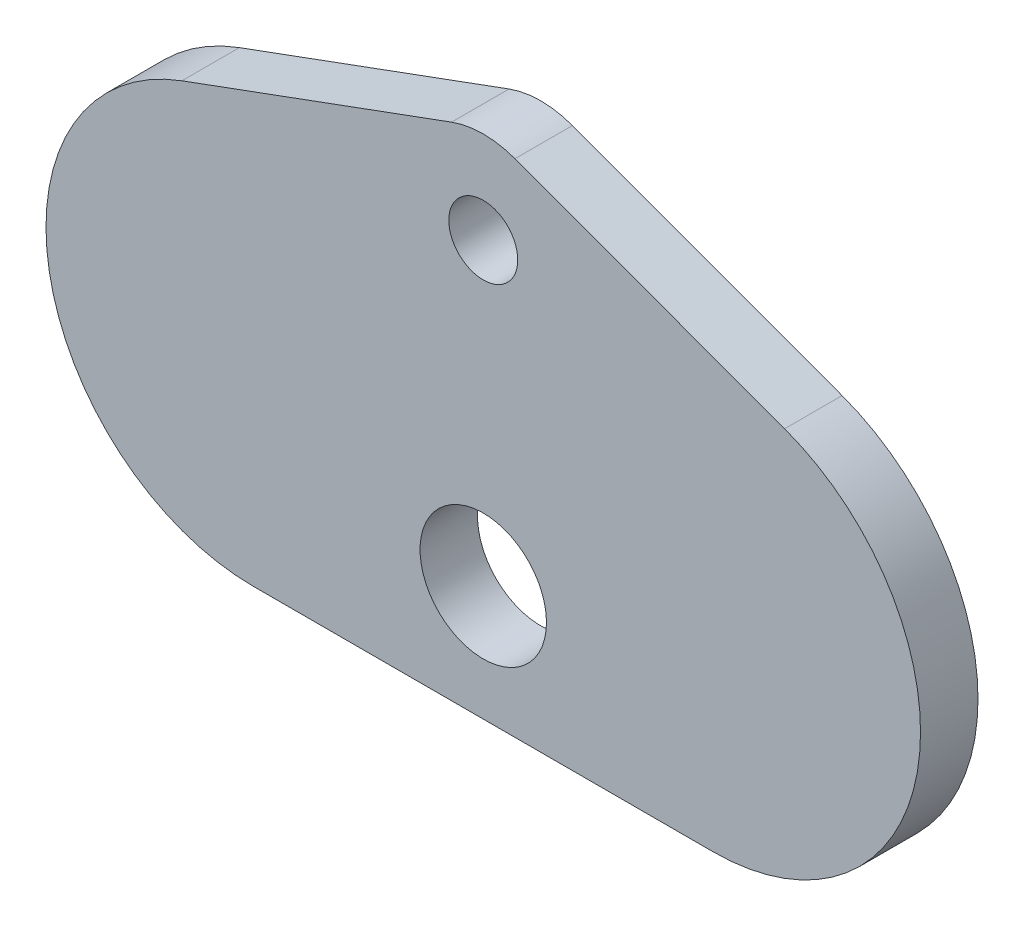
SolidWorks part; units mm, degrees
ref_plane "Płaszczyzna przednia" through (0, 0, 0) normal (0, 0, 1) x (1, 0, 0)
ref_plane "Płaszczyzna górna" through (0, 0, 0) normal (0, 1, 0) x (1, 0, 0)
ref_plane "Płaszczyzna prawa" through (0, 0, 0) normal (1, 0, 0) x (0, 0, -1)
sketch "Sketch1" plane through (0, 0, 0) normal (0, 0, 1) x (1, 0, 0)
  line L0 (-40, -52.095) -> (40, -52.095) construction
  line L1 (0, -52.095) -> (0, 0) construction
  line L2 (-40, -52.095) -> (40, -52.095) construction
  line L3 (-40, -16) -> (40, -16)
  line L4 (-40, -88.19) -> (40, -88.19)
  line L5 (-5.5152, -0.9806) -> (-52.4418, -18.2121)
  line L6 (5.5152, -0.9806) -> (52.4418, -18.2121)
  circle A0 centre (-40, -52.095) radius 26.095
  circle A1 centre (40, -52.095) radius 26.095
  circle A4 centre (0, -16) radius 6
  arc A7 (-40, -16) -> (-40, -88.19) centre (-40, -52.095) ccw
  arc A8 (40, -88.19) -> (40, -16) centre (40, -52.095) ccw
  circle A9 centre (0, -16) radius 16
  circle A10 centre (0, -68.1318) radius 11
  point P3 (0, -13)
  point P9 (0, -52.095)
  dimension "D1" = 52.19
  dimension "D2" = 52.19
  dimension "D3" = 12
  dimension "D4" = 10
  dimension "D5" = 10
  dimension "D6" = 22
  dimension "D7" = 40
  dimension "D9" = 43.095
  dimension "D8" = 80
extrude "Boss-Extrude1" add sketch "Sketch1" along normal blind 10 contours A9 L3 A7 L4 A8 A10 A0 A1 | A9 L3 A8 L6 | A9 L5 A7 L3 | L3 A9 A4 | L3 A9 A4 | A0 | A1 region at (0, -8.5149, 0) region at (0, -23.4851, 0) region at (24.9466, -11.6433, 0) region at (0, -53.2781, 0) region at (-24.9466, -11.6433, 0) region at (-40, -52.095, 0) region at (40, -52.095, 0)
